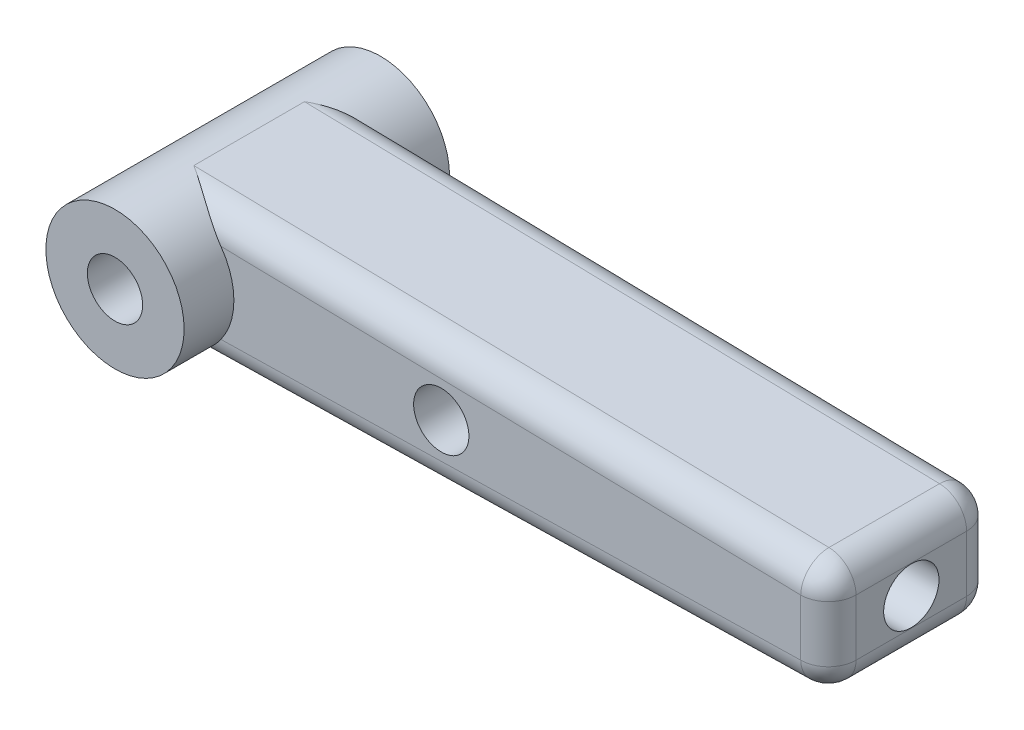
SolidWorks part; units mm, degrees
ref_plane "前视基准面" through (0, 0, 0) normal (0, 0, 1) x (1, 0, 0)
ref_plane "上视基准面" through (0, 0, 0) normal (0, 1, 0) x (1, 0, 0)
ref_plane "右视基准面" through (0, 0, 0) normal (1, 0, 0) x (0, 0, -1)
other "Configuration Table"
sketch "草图1" plane through (0, 0, 0) normal (0, 0, 1) x (1, 0, 0)
  circle A0 centre (0, 0) radius 0.5
  circle A1 centre (0, 0) radius 1.25
  dimension "D1" = 1
  dimension "D2" = 2.5
extrude "凸台-拉伸1" add sketch "草图1" along normal blind 4.8
ref_plane "基准面1" through (0, 0, 2.4) normal (0, 0, 1) x (1, 0, 0)
sketch "草图2" plane through (0, 0, 2.4) normal (0, 0, 1) x (1, 0, 0)
  line L0 (0, 0) -> (11.9791, 0) construction
  line L4 (0.0261, 1.2497) -> (12, 0.9998)
  line L5 (0.0261, -1.2497) -> (12, -0.9998)
  line L6 (12, 0.9998) -> (12, -0.9998)
  arc A0 (0.0261, -1.2497) -> (0.0261, 1.2497) centre (0, 0) ccw
  arc A1 (12, -0.9998) -> (12, 0.9998) centre (11.9791, 0) ccw construction
  dimension "D2" = 1.25
  dimension "D1" = 2
  dimension "D3" = 12
extrude "凸台-拉伸2" add sketch "草图2" along normal mid plane 3
sketch "草图3" plane through (0, 0, 3.9) normal (0, 0, 1) x (1, 0, 0)
  line L0 (0, 0) -> (10.2823, 0) construction
  circle A0 centre (5, 0) radius 0.5
  dimension "D2" = 1
  dimension "D1" = 5
extrude "切除-拉伸1" cut sketch "草图3" against normal blind 10
sketch "草图4" plane through (12, 0, 0) normal (1, 0, 0) x (0, 0, -1)
  line L0 (-3.9, 0) -> (-0.9, 0) construction
  line L1 (-3.9, -0.9998) -> (-3.9, 0.9998) construction
  line L2 (-0.9, -0.9998) -> (-0.9, 0.9998) construction
  circle A0 centre (-2.4, 0) radius 0.5
  dimension "D1" = 1
extrude "切除-拉伸2" cut sketch "草图4" against normal blind 5
fillet "圆角1" radius 0.5 8 edges at (6.013, -1.1248, 3.9) (6.013, -1.1248, 0.9) (6.013, 1.1248, 0.9) (6.013, 1.1248, 3.9) (12, 0, 0.9) (12, 0, 3.9) (12, -0.9998, 2.4) (12, 0.9998, 2.4)
